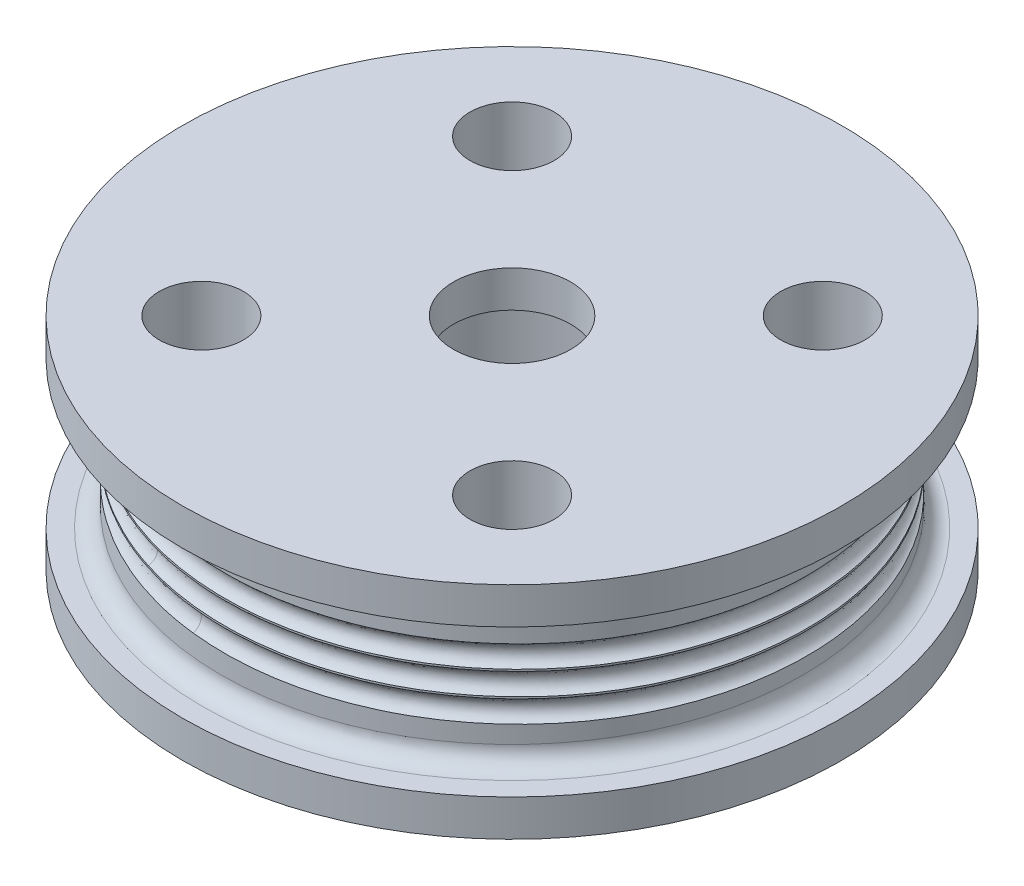
SolidWorks part; units mm, degrees
ref_plane "Front Plane" through (0, 0, 0) normal (0, 0, 1) x (1, 0, 0)
ref_plane "Top Plane" through (0, 0, 0) normal (0, 1, 0) x (1, 0, 0)
ref_plane "Right Plane" through (0, 0, 0) normal (1, 0, 0) x (0, 0, -1)
sketch "Sketch1" plane through (0, 0, 0) normal (0, 1, 0) x (1, 0, 0)
  circle A0 centre (0, 0) radius 9
  dimension "D1" = 18
extrude "Boss-Extrude1" add sketch "Sketch1" along normal blind 1
sketch "Sketch2" plane through (0, 1, 0) normal (0, 1, 0) x (1, 0, 0)
  circle A0 centre (0, 0) radius 7.95
  dimension "D1" = 15.9
extrude "Boss-Extrude2" add sketch "Sketch2" along normal blind 4.02
sketch3d "3DSketch1" plane through (0, 0, 0) normal (0, 0, 1) x (1, 0, 0)
  dimension "D1" = 1.035
sketch "Sketch6" plane through (0, 2.035, 0) normal (0, 1, 0) x (1, 0, 0)
  circle A0 centre (0, 0) radius 8.075
  dimension "D1" = 16.15
curve "Helix/Spiral1" pitch 0.65 height 1.95 radius 8.075 left hand yes centre (0, 2.035, 0) axis (0, 1, 0) start towards (0, 0, -1)
sweep "Cut-Sweep1" cut path "Helix/Spiral1" align with end faces yes circular profile diameter 0.65 parameters "D3"=0.65
sketch "Sketch4" plane through (0, 5.02, 0) normal (0, 1, 0) x (1, 0, 0)
  circle A0 centre (0, 0) radius 9
sketch "Sketch58" plane through (0, 0, 0) normal (0, -1, 0) x (1, 0, 0)
  line L0 (0, 0) -> (-8.344, 0) construction
  line L1 (0, 0) -> (-6.364, -6.364) construction
  circle A0 centre (0, 0) radius 9 construction
  dimension "D1" = 45
sketch "Sketch68" plane through (0, 5.02, 0) normal (0, 1, 0) x (1, 0, 0)
  circle A0 centre (0, 0) radius 9 construction
  circle A1 centre (0, 0) radius 9
extrude "Boss-Extrude4" add sketch "Sketch68" along normal blind 1
fillet "Fillet2" radius 0.5 2 edges at (0, 5.02, 7.95) (0, 1, 7.95)
sketch "Sketch3" plane through (0, 0, 0) normal (0, -1, 0) x (1, 0, 0)
  line L0 (0, 0) -> (-4.2426, 4.2426) construction
  line L1 (0, 0) -> (-6, 0) construction
  circle A0 centre (0, 0) radius 6 construction
  circle A1 centre (-4.2426, 4.2426) radius 1.15
  circle A5 centre (4.2426, 4.2426) radius 1.15
  circle A6 centre (4.2426, -4.2426) radius 1.15
  circle A7 centre (-4.2426, -4.2426) radius 1.15
  point P13 (-3, 1.2426)
  point P15 (0, 0)
  dimension "D1" = 12
  dimension "D2" = 2.3
  dimension "D4" = 45
  dimension "D3" = 4
extrude "Cut-Extrude1" cut sketch "Sketch3" against normal through all
sketch "Sketch72" plane through (0, 0, 0) normal (0, 1, 0) x (1, 0, 0)
  circle A0 centre (0, 0) radius 1.6
  dimension "D1" = 3.2
extrude "Cut-Extrude3" cut sketch "Sketch72" along normal up to surface (6.02 mm away) up to face at (-4.2426, 6.02, -5.3926)
sketch "Sketch73" plane through (0, 0, 0) normal (0, 1, 0) x (1, 0, 0)
  circle A0 centre (0, 0) radius 2.8
  dimension "D1" = 5.6
extrude "Cut-Extrude4" cut sketch "Sketch73" along normal offset from surface (5.02 mm away) 1 up to face at (0, 6.02, 1.6)
sketch "Sketch74" plane through (0, 0, 0) normal (0, 0, 1) x (1, 0, 0)
  line L0 (0, 0) -> (0, 7.209) construction
  line L1 (-9, 5.02) -> (9, 5.02) construction
  line L2 (-2.8, 0) -> (2.8, 0) construction
  line L3 (-2.8, 0) -> (2.8, 0) construction
  line L4 (2.8, 0) -> (2.8, 7.8897) construction
  circle A0 centre (2.2, 4.27) radius 0.6
  dimension "D2" = 1.2
  dimension "D1" = 0.75
ref_plane "Plane3" through (0, 3.01, 0) normal (0, 1, 0) x (1, 0, 0)
ref_plane "Plane4" through (0, 0, -8) normal (0, 0, 1) x (1, 0, 0)
sketch "Sketch78" plane through (0, 0, -8) normal (0, 0, 1) x (1, 0, 0)
  circle A1 centre (-0.0038, 4.285) radius 0.6
  dimension "D1" = 1.2
loft "Cut-Loft1" cut profiles "Sketch74", "Sketch78" connector at (2.8, 4.27, 0) connector at (0.5962, 4.285, -8)
sketch "Sketch75" plane through (0, 3.01, 0) normal (0, 1, 0) x (1, 0, 0)
  line L0 (0, 0) -> (8, 0) construction
  line L1 (8, 0) -> (8, 35) construction
  line L2 (8, 35) -> (13.75, 35) construction
  line L3 (13.75, 35) -> (13.75, 29.25) construction
  line L4 (13.75, 29.25) -> (96.9647, 29.25) construction
  circle A0 centre (0, 0) radius 8 construction
  circle A1 centre (13.75, 35) radius 5.75 construction
  dimension "D1" = 11.5
  dimension "D2" = 35
  dimension "D3" = 8
  dimension "D4" = 5.75
